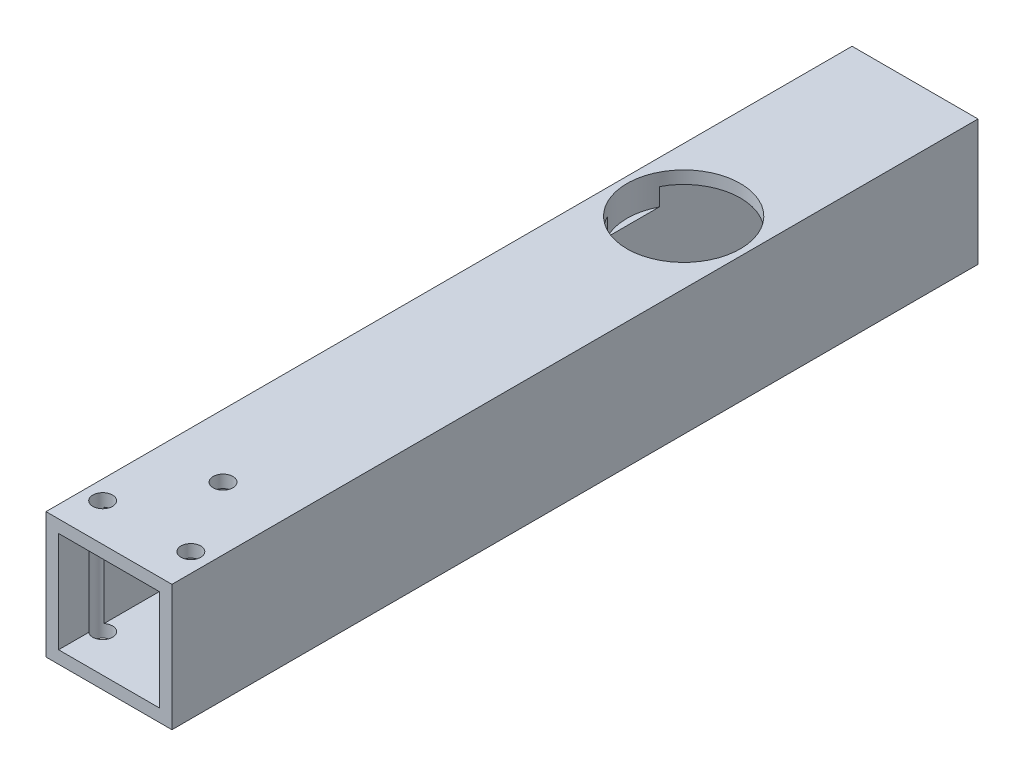
SolidWorks part; units mm, degrees
ref_plane "Front Plane" through (0, 0, 0) normal (0, 0, 1) x (1, 0, 0)
ref_plane "Top Plane" through (0, 0, 0) normal (0, 1, 0) x (1, 0, 0)
ref_plane "Right Plane" through (0, 0, 0) normal (1, 0, 0) x (0, 0, -1)
sketch "Sketch1" plane through (0, 0, 0) normal (0, 0, 1) x (1, 0, 0)
  line L0 (-12.7, 12.7) -> (12.7, 12.7)
  line L2 (-15.875, 15.875) -> (15.875, 15.875)
  line L3 (-15.875, 15.875) -> (-15.875, -15.875)
  line L4 (-15.875, -15.875) -> (15.875, -15.875)
  line L5 (15.875, 15.875) -> (15.875, -15.875)
  line L10 (12.7, 12.7) -> (12.7, -12.7)
  line L11 (-12.7, -12.7) -> (12.7, -12.7)
  line L12 (-12.7, 12.7) -> (-12.7, -12.7)
  point P12 (0, 15.875)
  point P14 (15.875, 0)
  dimension "Wall Thickness" = 3.175
  dimension "Outside Width" = 31.75
  dimension "Outside Height" = 31.75
  dimension "Inside Height" = 25.4
  dimension "Inside Width" = 25.4
sketch "Sketch2" plane through (0, 0, 0) normal (1, 0, 0) x (0, 0, -1)
  line L0 (101.6, 0) -> (-101.6, 0)
  point P4 (0, 0)
  point P7 (-101.6, 0)
  point P10 (101.6, 0)
  dimension "Length" = 203.2
sketch "Sketch3" plane through (0, 0, 0) normal (0, 0, 1) x (1, 0, 0)
  line L21 (15.875, 15.875) -> (-15.875, 15.875)
  line L22 (15.875, -15.875) -> (15.875, 15.875)
  line L23 (-15.875, -15.875) -> (15.875, -15.875)
  line L24 (-15.875, 15.875) -> (-15.875, -15.875)
  line L25 (15.875, 15.875) -> (-15.875, 15.875)
  line L26 (15.875, -15.875) -> (15.875, 15.875)
  line L27 (-15.875, -15.875) -> (15.875, -15.875)
  line L28 (-15.875, 15.875) -> (-15.875, -15.875)
  line L29 (12.7, 12.7) -> (-12.7, 12.7)
  line L30 (12.7, -12.7) -> (12.7, 12.7)
  line L31 (-12.7, -12.7) -> (12.7, -12.7)
  line L32 (-12.7, 12.7) -> (-12.7, -12.7)
  line L33 (12.7, 12.7) -> (-12.7, 12.7)
  line L34 (12.7, -12.7) -> (12.7, 12.7)
  line L35 (-12.7, -12.7) -> (12.7, -12.7)
  line L36 (-12.7, 12.7) -> (-12.7, -12.7)
  dimension "D1" = 0
  dimension "D2" = 0
extrude "Boss-Extrude1" add sketch "Sketch3" along normal up to vertex (101.6 mm away) and the other way up to vertex (101.6 mm away) up to point (0, 0, 101.6) other way up to point (0, 0, -101.6)
sketch "Drawing Reference" plane through (0, 0, 0) normal (1, 0, 0) x (0, 0, -1)
  line L0 (-101.6, 0) -> (101.6, 0) construction
  line L1 (0, -15.875) -> (0, 15.875) construction
  line L2 (-101.6, -15.875) -> (101.6, -15.875) construction
  line L5 (-101.6, 15.875) -> (101.6, 15.875) construction
  point P7 (-78.74, 0)
  point P8 (78.74, 0)
  dimension "D1" = 22.86
sketch "Sketch4" plane through (0, 15.875, 0) normal (0, 1, 0) x (1, 0, 0)
  line L0 (0, -101.6) -> (0, -92.075) construction
  line L1 (15.875, -101.6) -> (-15.875, -101.6) construction
  line L2 (0, -92.075) -> (11.1125, -92.075) construction
  line L3 (0, -92.075) -> (-11.1125, -92.075) construction
  line L4 (0, -92.075) -> (0, 43.2816) construction
  line L5 (0, -92.075) -> (0, -98.2472) construction
  dimension "D1" = 135.3566
  dimension "D2" = 22.225
  dimension "D3" = 9.525
hole_wizard "#10 Clearance Hole1" positions "Sketch5" profile "Sketch6" hole size "#10" standard "ANSI Inch" end condition through all
sketch "Sketch5" plane through (0, 15.875, 0) normal (0, 1, 0) x (1, 0, 0)
  point P0 (-11.1125, -92.075)
  point P3 (11.1125, -92.075)
  point P7 (0, -72.8472)
sketch "Sketch6" plane through (-11.1125, 15.875, 92.075) normal (1, 0, 0) x (0, 0, 1)
  line L0 (0, 0) -> (0, 31.75)
  line L1 (0, 31.75) -> (2.4892, 31.75)
  line L2 (2.4892, 31.75) -> (2.4892, 0)
  line L5 (2.4892, 0) -> (0, 0)
  line L11 (0, -6.35) -> (0, 107.95) construction
  dimension "Thru Hole Dia." = 4.9784
  dimension "Thru Hole Depth" = 31.75
sketch "Sketch7" plane through (0, 15.875, 0) normal (0, 1, 0) x (1, 0, 0)
  circle A0 centre (0, 43.2816) radius 14.2875
  dimension "D1" = 28.575
extrude "Cut-Extrude1" cut sketch "Sketch7" against normal blind 7.62
sketch "Sketch8" plane through (0, -15.875, 0) normal (0, -1, 0) x (1, 0, 0)
  circle A0 centre (0, -43.2816) radius 14.2875
  dimension "D1" = 28.575
extrude "Cut-Extrude2" cut sketch "Sketch8" against normal blind 7.62
equation "\"D1@Drawing Reference\"=\"Outside Width@Sketch1\" * 0.72"
